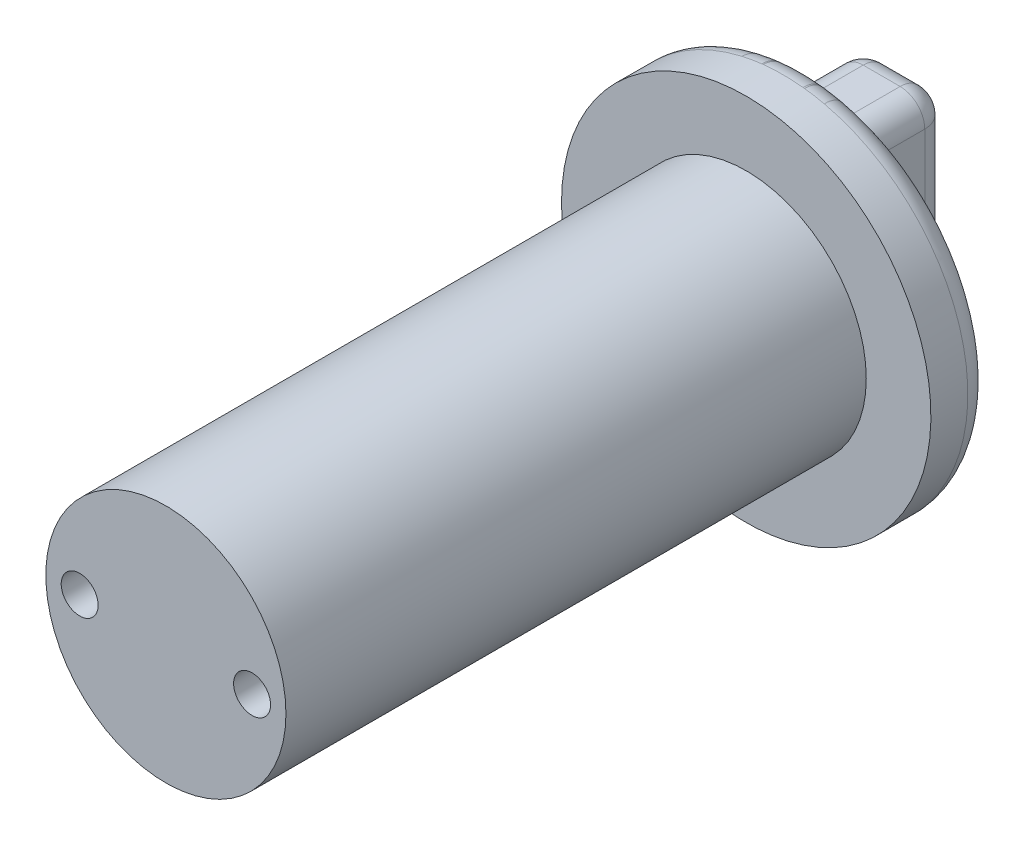
SolidWorks part; units mm, degrees
material "6061 Alloy"
ref_plane "Front Plane" through (0, 0, 0) normal (0, 0, 1) x (1, 0, 0)
ref_plane "Top Plane" through (0, 0, 0) normal (0, 1, 0) x (1, 0, 0)
ref_plane "Right Plane" through (0, 0, 0) normal (1, 0, 0) x (0, 0, -1)
sketch "Sketch1" plane through (0, 0, 0) normal (0, 0, 1) x (1, 0, 0)
  circle A0 centre (0, 0) radius 9.75
  dimension "D1" = 19.5
extrude "Boss-Extrude1" add sketch "Sketch1" along normal blind 47.125
sketch "Sketch2" plane through (0, 0, 0) normal (0, 0, -1) x (-1, 0, 0)
  circle A0 centre (0, 0) radius 15
  dimension "D1" = 30
extrude "Boss-Extrude2" add sketch "Sketch2" along normal blind 5
sketch "Sketch3" plane through (0, 0, -5) normal (0, 0, -1) x (-1, 0, 0)
  line L1 (-3.5, 10.9245) -> (3.5, 10.9245)
  line L2 (-3.5, 10.9245) -> (-3.5, -10.9245)
  line L3 (-3.5, -10.9245) -> (3.5, -10.9245)
  line L4 (3.5, 10.9245) -> (3.5, -10.9245)
  line L5 (0, -10.9245) -> (0, 10.9245) construction
  line L6 (-3.5, 0) -> (3.5, 0) construction
  point P0 (0, 0)
  dimension "D1" = 7
extrude "Boss-Extrude4" add sketch "Sketch3" along normal blind 8
fillet "Fillet1" radius 2 12 edges at (-3.5, 0, -5) (-3.5, 10.9245, -9) (0, 10.9245, -5) (3.5, 10.9245, -9) (3.5, 0, -5) (3.5, -10.9245, -9) (-3.5, -10.9245, -9) (0, -10.9245, -5) (0, -10.9245, -13) (3.5, 0, -13) (0, 10.9245, -13) (-3.5, 0, -13)
fillet "Fillet2" radius 2 1 edges at (-15, 0, -5)
sketch "Sketch4" plane through (0, 0, 47.125) normal (0, 0, 1) x (1, 0, 0)
  line L0 (0, 0) -> (-7, 0) construction
  line L1 (0, 0) -> (0, -4.7782) construction
  circle A0 centre (-7, 0) radius 1.5
  circle A1 centre (7, 0) radius 1.5
  dimension "D1" = 3
  dimension "D2" = 7
extrude "M4_DRILL" cut sketch "Sketch4" against normal blind 8
